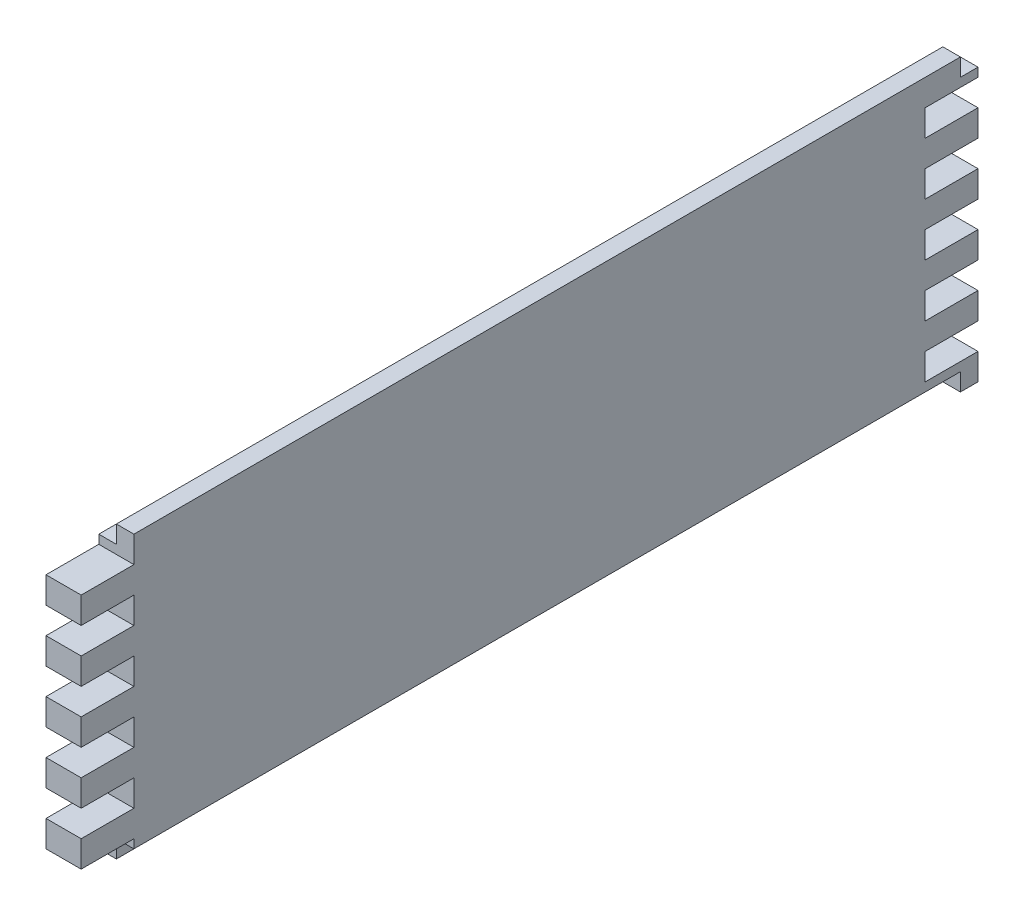
SolidWorks part; units mm, degrees
material "Сосна"
ref_plane "Спереди" through (0, 0, 0) normal (0, 0, 1) x (1, 0, 0)
ref_plane "Сверху" through (0, 0, 0) normal (0, 1, 0) x (1, 0, 0)
ref_plane "Справа" through (0, 0, 0) normal (1, 0, 0) x (0, 0, -1)
sketch "Эскиз1" plane through (0, 0, 0) normal (0, 0, 1) x (1, 0, 0)
  line L0 (0, 0) -> (0, 155)
  line L1 (0, 155) -> (10, 155)
  line L2 (10, 155) -> (10, 165)
  line L3 (10, 165) -> (20, 165)
  line L4 (20, 165) -> (20, 10)
  line L5 (20, 10) -> (10, 10)
  line L6 (10, 10) -> (10, 0)
  line L7 (10, 0) -> (0, 0)
  dimension "D1" = 155
  dimension "D2" = 10
  dimension "D3" = 10
  dimension "D4" = 20
  dimension "D5" = 10
  dimension "D6" = 10
extrude "Бобышка-Вытянуть1" add sketch "Эскиз1" along normal blind 450
sketch "Эскиз2" plane through (20, 0, 0) normal (1, 0, 0) x (0, 0, -1)
  line L2 (-450, 10) -> (-450, 165) construction
  line L3 (-450, 150) -> (-480, 150)
  line L4 (-450, 150) -> (-450, 135)
  line L5 (-450, 135) -> (-480, 135)
  line L6 (-480, 150) -> (-480, 135)
  line L7 (-450, 165) -> (0, 165) construction
  dimension "D1" = 15
  dimension "D2" = 30
  dimension "D3" = 15
extrude "Бобышка-Вытянуть2" add sketch "Эскиз2" against normal up to surface (20 mm away) up to face at (0, 77.5, 225)
pattern_linear "Линейный массив1" count 1 spacing 50 along (0, 0, 1) count 5 spacing 30 along (0, -1, 0) of "Бобышка-Вытянуть2"
sketch "Эскиз3" plane through (20, 0, 0) normal (1, 0, 0) x (0, 0, -1)
  line L1 (0, 165) -> (30, 165)
  line L2 (0, 165) -> (0, 150)
  line L3 (0, 150) -> (30, 150)
  line L4 (30, 165) -> (30, 150)
  dimension "D1" = 15
  dimension "D2" = 30
extrude "Бобышка-Вытянуть3" add sketch "Эскиз3" against normal up to surface (20 mm away) up to face at (0, 83.3333, 425)
pattern_linear "Линейный массив2" count 1 spacing 50 along (0, 0, 1) count 6 spacing 30 along (0, -1, 0) of "Бобышка-Вытянуть3"
sketch "Эскиз4" plane through (0, 0, 0) normal (0, 0, 1) x (1, 0, 0)
  line L1 (0, 165) -> (10, 165)
  line L2 (0, 165) -> (0, 155)
  line L3 (0, 155) -> (10, 155)
  line L4 (10, 165) -> (10, 155)
extrude "Вырез-Вытянуть1" cut sketch "Эскиз4" against normal blind 20
sketch "Эскиз5" plane through (0, 0, 0) normal (0, 0, 1) x (1, 0, 0)
  line L1 (20, 10) -> (10, 10)
  line L2 (20, 10) -> (20, 0)
  line L3 (20, 0) -> (10, 0)
  line L4 (10, 10) -> (10, 0)
extrude "Вырез-Вытянуть2" cut sketch "Эскиз5" against normal blind 20
sketch "Эскиз6" plane through (0, 0, 0) normal (-1, 0, 0) x (0, 0, 1)
  line L1 (-30, 165) -> (-20, 165)
  line L2 (-30, 165) -> (-30, 155)
  line L3 (-30, 155) -> (-20, 155)
  line L4 (-20, 165) -> (-20, 155)
extrude "Вырез-Вытянуть3" cut sketch "Эскиз6" against normal blind 20
